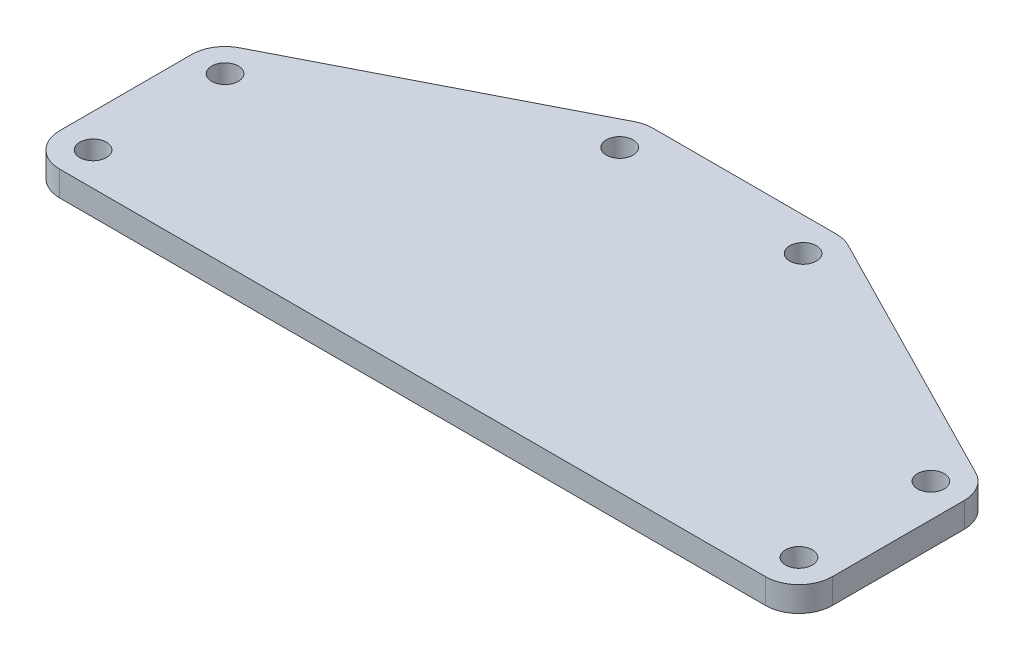
SolidWorks part; units mm, degrees
ref_plane "Front Plane" through (0, 0, 0) normal (0, 0, 1) x (1, 0, 0)
ref_plane "Top Plane" through (0, 0, 0) normal (0, 1, 0) x (1, 0, 0)
ref_plane "Right Plane" through (0, 0, 0) normal (1, 0, 0) x (0, 0, -1)
sketch "Sketch1" plane through (0, 0, 0) normal (0, 1, 0) x (1, 0, 0)
  line L0 (0, 0) -> (0, 20.4742) construction
  line L1 (-42.325, -31.825) -> (-42.325, -16) construction
  line L2 (11, 0) -> (-11, 0) construction
  line L3 (-46.325, -31.825) -> (-46.325, -16)
  line L4 (-44.1445, -12.4378) -> (-12.8195, 3.5622)
  line L5 (44.1445, -12.4378) -> (12.8195, 3.5622)
  line L6 (46.325, -31.825) -> (46.325, -16)
  line L7 (-11, 4) -> (11, 4)
  line L8 (-42.325, -35.825) -> (42.325, -35.825)
  circle A0 centre (-42.325, -31.825) radius 1.6
  circle A1 centre (-42.325, -16) radius 1.6
  circle A2 centre (42.325, -31.825) radius 1.6
  circle A3 centre (42.325, -16) radius 1.6
  circle A4 centre (-11, 0) radius 1.6
  circle A5 centre (11, 0) radius 1.6
  arc A6 (-11, 4) -> (-12.8195, 3.5622) centre (-11, 0) ccw
  arc A7 (-44.1445, -12.4378) -> (-46.325, -16) centre (-42.325, -16) ccw
  arc A8 (-46.325, -31.825) -> (-42.325, -35.825) centre (-42.325, -31.825) ccw
  arc A9 (46.325, -31.825) -> (42.325, -35.825) centre (42.325, -31.825) cw
  arc A10 (44.1445, -12.4378) -> (46.325, -16) centre (42.325, -16) cw
  arc A11 (11, 4) -> (12.8195, 3.5622) centre (11, 0) cw
  point P15 (0, 0)
  point P28 (40.8145, -35.5288)
  dimension "D1" = 3.2
  dimension "D6" = 4
  dimension "D2" = 15.825
  dimension "D3" = 84.65
  dimension "D4" = 22
  dimension "D5" = 35.1746
extrude "Boss-Extrude1" add sketch "Sketch1" along normal blind 3
